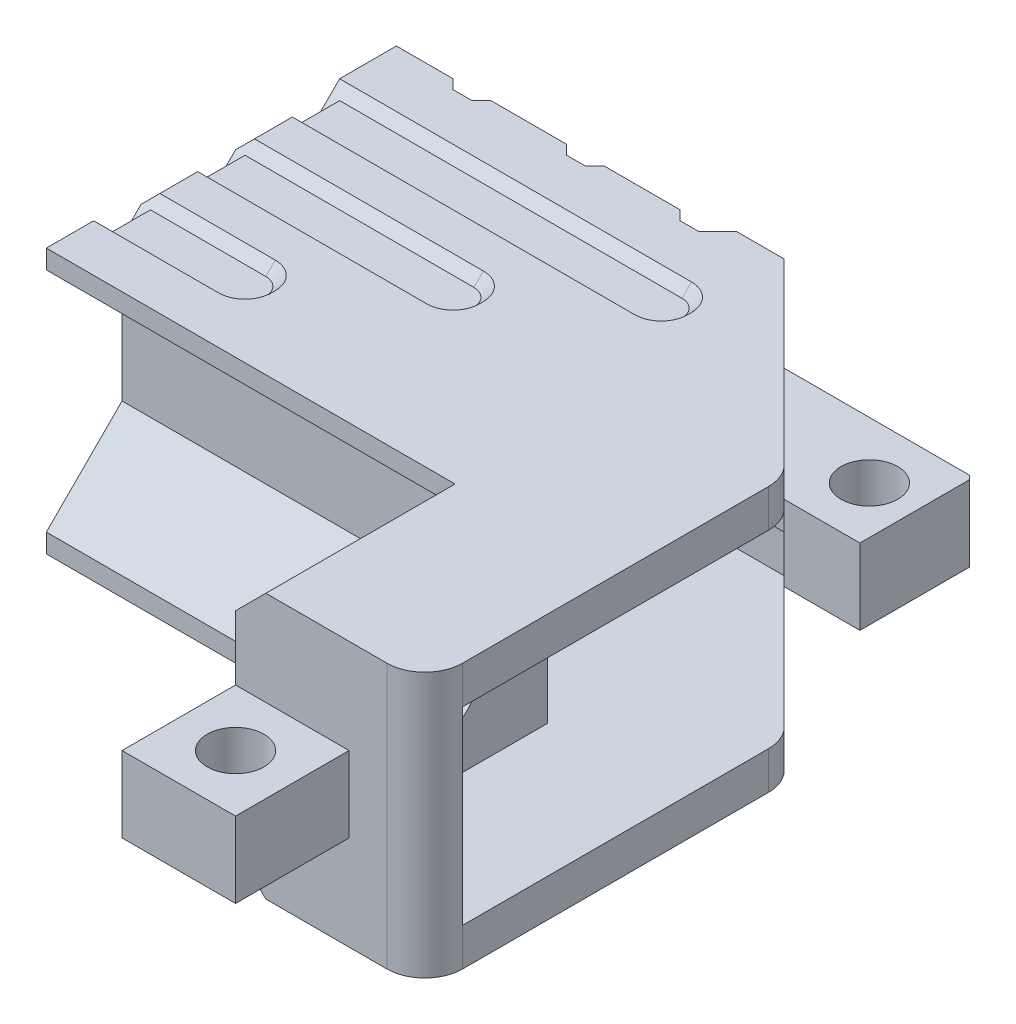
SolidWorks part; units mm, degrees
note: The reader was unsure of these and kept them because the rebuilt part matched: shared geometry of "草图9<2>".
ref_plane "前视基准面" through (0, 0, 0) normal (0, 0, 1) x (1, 0, 0)
ref_plane "上视基准面" through (0, 0, 0) normal (0, 1, 0) x (1, 0, 0)
ref_plane "右视基准面" through (0, 0, 0) normal (1, 0, 0) x (0, 0, -1)
sketch "草图1" plane through (0, 0, 0) normal (0, 1, 0) x (1, 0, 0)
  line L0 (20, 15) -> (30, 5)
  line L1 (0, 0) -> (20, 0)
  line L2 (0, 0) -> (0, 15)
  line L3 (0, 15) -> (20, 15)
  line L4 (30, -14) -> (30, 5)
  line L7 (30, -14) -> (20, -14)
  line L8 (20, 0) -> (20, -14)
  point P1 (30, 15)
  dimension "D1" = 29
  dimension "D2" = 15
  dimension "D3" = 20
  dimension "D4" = 10
extrude "凸台-拉伸1" add sketch "草图1" along normal blind 14
sketch "草图2" plane through (20, 0, 0) normal (-1, 0, 0) x (0, 0, 1)
  line L0 (14, 14) -> (14, 0) construction
  line L1 (0, 14) -> (14, 14) construction
  line L2 (4.2, 5.4508) -> (4.2, 8.5492)
  arc A0 (4.2, 5.4508) -> (4.2, 8.5492) centre (7, 7) ccw
  dimension "D1" = 6.4
  dimension "D2" = 7
  dimension "D3" = 7
  dimension "D4" = 2.8
extrude "切除-拉伸1" cut sketch "草图2" against normal blind 3
chamfer "倒角1" distance 1.6 angle 45 2 edges at (20, 0, 7) (20, 14, 7)
sketch "草图3" plane through (0, 14, 0) normal (0, 1, 0) x (1, 0, 0)
  line L1 (20, -14) -> (26, -14)
  line L2 (20, -14) -> (20, -20)
  line L3 (20, -20) -> (26, -20)
  line L4 (26, -14) -> (26, -20)
  dimension "D1" = 6
  dimension "D2" = 6
extrude "凸台-拉伸3" add sketch "草图3" against normal blind 4 from offset 5 offset against normal yes
sketch "草图4" plane through (0, 0, 0) normal (-1, 0, 0) x (0, 0, 1)
  line L0 (0, 14) -> (0, 0) construction
  line L1 (-15, 14) -> (0, 14) construction
  line L2 (-10.3, 5.4508) -> (-10.3, 8.5492)
  arc A0 (-10.3, 5.4508) -> (-10.3, 8.5492) centre (-7.5, 7) ccw
  dimension "D1" = 6.4
  dimension "D2" = 7.5
  dimension "D3" = 7
  dimension "D4" = 2.8
extrude "切除-拉伸2" cut sketch "草图4" against normal blind 3.4
sketch "草图5" plane through (0, 14, 0) normal (0, 1, 0) x (1, 0, 0)
  line L0 (30, -14) -> (30, 5) construction
  line L1 (3, 2.5) -> (23, 2.5)
  line L2 (3, 2.5) -> (3, 12.5)
  line L3 (3, 12.5) -> (30, 12.5)
  line L4 (30, -12) -> (30, 12.5)
  line L5 (23, -12) -> (30, -12)
  line L6 (23, -12) -> (23, 2.5)
  line L9 (20, 15) -> (0, 15) construction
  line L10 (0, 0) -> (21.6, 0) construction
  line L11 (0, 15) -> (0, 0) construction
  line L12 (21.6, -14) -> (30, -14) construction
  line L13 (20, -14) -> (20, 0) construction
  dimension "D1" = 2.5
  dimension "D2" = 2.5
  dimension "D3" = 3
  dimension "D4" = 2
  dimension "D6" = 3
extrude "切除-拉伸3" cut sketch "草图5" against normal blind 10 from offset 2 offset against normal yes
sketch "草图6" plane through (0, 14, 0) normal (0, 1, 0) x (1, 0, 0)
  line L0 (22.5, 12.5) -> (3, 12.5) construction
  line L5 (23.5, 11.5) -> (19, 11.5)
  line L6 (20, 15) -> (30, 15)
  line L8 (26, 9) -> (30, 9)
  line L9 (30, 15) -> (30, 9)
  line L10 (0, 15) -> (0, 0) construction
  line L11 (30, 5) -> (20, 15) construction
  line L12 (26, 9) -> (23.5, 11.5)
  line L16 (22.5, 12.5) -> (18, 12.5)
  line L17 (18, 12.5) -> (19, 11.5)
  line L18 (22.5, 12.5) -> (20, 15)
  dimension "D1" = 1
  dimension "D2" = 6
  dimension "D3" = 2
  dimension "D4" = 30
  dimension "D5" = 45
extrude "凸台-拉伸4" add sketch "草图6" against normal blind 4 from offset 5 contours L8 L9 L6 L18 L16 L17 L5 L12 offset against normal yes
chamfer "倒角2" distance 3 angle 45 1 edges at (23, 7, -2.5)
sketch "草图7" plane through (0, 14, 0) normal (0, 1, 0) x (1, 0, 0)
  line L2 (20, -14) -> (20, -20) construction
  line L3 (20, -20) -> (26, -20) construction
  line L4 (20, 15) -> (30, 15) construction
  line L6 (30, 15) -> (30, 9) construction
  circle A0 centre (27.5, 12) radius 1.5
  circle A1 centre (23, -17) radius 1.5
  dimension "D1" = 3
  dimension "D5" = 3
  dimension "D6" = 3
  dimension "D2" = 2.5
  dimension "D3" = 3
  dimension "D4" = 3
extrude "切除-拉伸4" cut sketch "草图7" against normal through all
chamfer "倒角3" distance 0.2 angle 45 1 edges at (30, 7, -15)
sketch "草图8" plane through (0, 14, 0) normal (0, 1, 0) x (1, 0, 0)
  line L0 (20, 15) -> (0, 15) construction
  line L1 (5.5, 15) -> (2.5, 15)
  line L2 (2.5, 15) -> (3, 14.5)
  line L3 (3, 14.5) -> (5, 14.5)
  line L4 (5, 14.5) -> (5.5, 15)
  line L5 (0, 15) -> (0, 0) construction
  line L6 (11.5, 15) -> (8.5, 15)
  line L7 (8.5, 15) -> (9, 14.5)
  line L8 (9, 14.5) -> (11, 14.5)
  line L9 (11, 14.5) -> (11.5, 15)
  line L10 (17.5, 15) -> (14.5, 15)
  line L11 (14.5, 15) -> (15, 14.5)
  line L12 (15, 14.5) -> (17, 14.5)
  line L13 (17, 14.5) -> (17.5, 15)
  line L14 (5.5, 15) -> (11.5, 15) construction
  dimension "D1" = 0.5
  dimension "D2" = 45
  dimension "D3" = 45
  dimension "D4" = 2
  dimension "D5" = 2.5
  dimension "D6" = 3
  dimension "D7" = 6
extrude "切除-拉伸5" cut sketch "草图8" against normal through all
chamfer "倒角5" distance 0.5 angle 45 6 edges at (4, 0, -14.5) (10, 0, -14.5) (16, 0, -14.5) (16, 14, -14.5) (10, 14, -14.5) (4, 14, -14.5)
sketch "草图15" plane through (0, 0, 0) normal (-1, 0, 0) x (0, 0, 1)
  line L0 (0, 14) -> (4, 14)
  line L2 (4, 13) -> (0, 9)
  line L3 (0, 14) -> (0, 0) construction
  line L5 (0, 0) -> (4, 0)
  line L6 (4, 1) -> (0, 5)
  line L7 (0, 14) -> (0, 9)
  line L8 (0, 5) -> (0, 0)
  line L9 (4, 14) -> (4, 13)
  line L10 (4, 1) -> (4, 0)
  line L12 (-15, 14) -> (0, 14) construction
  dimension "D1" = 5
  dimension "D2" = 45
  dimension "D3" = 45
  dimension "D4" = 5
  dimension "D5" = 4
extrude "凸台-拉伸5" add sketch "草图15" against normal blind 22
sketch "草图9" plane through (0, 14, 0) normal (0, 1, 0) x (1, 0, 0)
  line L0 (0, 15) -> (0, -4) construction
  line L5 (0, 0) -> (21.6, 0) construction
  line L6 (0, 3.5) -> (12.6, 3.5)
  line L7 (0, 3.5) -> (0, 6.5)
  line L8 (0, 6.5) -> (12.6, 6.5)
  line L9 (14, 4.9) -> (14, 5.1)
  line L18 (0, 8.5) -> (18.6, 8.5)
  line L19 (0, 8.5) -> (0, 11.5)
  line L20 (0, 11.5) -> (18.6, 11.5)
  line L21 (20, 9.9) -> (20, 10.1)
  line L22 (0, -1.5) -> (6.6, -1.5)
  line L23 (0, -1.5) -> (0, 1.5)
  line L24 (0, 1.5) -> (6.6, 1.5)
  line L25 (8, -0.1) -> (8, 0.1)
  line L26 (0, 15) -> (0, -4) construction
  arc A0 (12.6, 3.5) -> (14, 4.9) centre (12.6, 4.9) ccw
  arc A1 (14, 5.1) -> (12.6, 6.5) centre (12.6, 5.1) ccw
  arc A2 (18.6, 8.5) -> (20, 9.9) centre (18.6, 9.9) ccw
  arc A3 (20, 10.1) -> (18.6, 11.5) centre (18.6, 10.1) ccw
  arc A4 (6.6, -1.5) -> (8, -0.1) centre (6.6, -0.1) ccw
  arc A5 (8, 0.1) -> (6.6, 1.5) centre (6.6, 0.1) ccw
  dimension "D7" = 1.4
  dimension "D12" = 1.4
  dimension "D1" = 3.5
  dimension "D2" = 3
  dimension "D3" = 2
  dimension "D4" = 3
  dimension "D5" = 14
  dimension "D6" = 20
  dimension "D8" = 3
  dimension "D9" = 0
  dimension "D10" = 2
  dimension "D11" = 8
extrude "切除-拉伸6" cut sketch "草图9" against normal blind 0.5
extrude "切除-拉伸7" cut sketch "草图9<2>" along normal blind 0.5 from surface at -14 starting at face at (12.8, 0, -9.1053)
sketch "草图9<2>" plane through (0, 14, 0) normal (0, 1, 0) x (1, 0, 0) same geometry as "草图9"
sketch "草图13" plane through (0, 0, 0) normal (-1, 0, 0) x (0, 0, 1)
  circle A0 centre (-7.5, 7) radius 5
  circle A1 centre (-7.5, 7) radius 5.4
  dimension "D1" = 10
  dimension "D2" = 10.8
extrude "切除-拉伸8" cut sketch "草图13" against normal blind 0.4
chamfer "倒角7" distance 0.4 angle 45 1 edges at (0, 7, -2.5)
chamfer "倒角8" distance 0.5 angle 45 30 edges at (6.3, 13.5, -3.5) (13.5899, 13.5, -3.9101) (14, 13.5, -5) (13.5899, 13.5, -6.0899) (6.3, 13.5, -6.5) (9.3, 13.5, -8.5) (19.5899, 13.5, -8.9101) (20, 13.5, -10) (19.5899, 13.5, -11.0899) (9.3, 13.5, -11.5) (6.3, 0.5, -3.5) (13.5899, 0.5, -3.9101) (14, 0.5, -5) (13.5899, 0.5, -6.0899) (6.3, 0.5, -6.5) (9.3, 0.5, -8.5) (19.5899, 0.5, -8.9101) (20, 0.5, -10) (19.5899, 0.5, -11.0899) (9.3, 0.5, -11.5) (3.3, 0.5, 1.5) (7.5899, 0.5, 1.0899) (8, 0.5, 0) (7.5899, 0.5, -1.0899) (3.3, 0.5, -1.5) (3.3, 13.5, 1.5) (7.5899, 13.5, 1.0899) (8, 13.5, 0) (7.5899, 13.5, -1.0899) (3.3, 13.5, -1.5)
chamfer "倒角6" distance 0.5 angle 45 6 edges at (13, 0, -15) (7, 0, -15) (1.25, 0, -15) (13, 14, -15) (7, 14, -15) (1.25, 14, -15)
chamfer "倒角9" distance 0.4 angle 45 1 edges at (0, 7, -2.1)
fillet "圆角1" radius 2 3 edges at (30, 1, -5) (30, 13, -5) (30, 7, 14)
